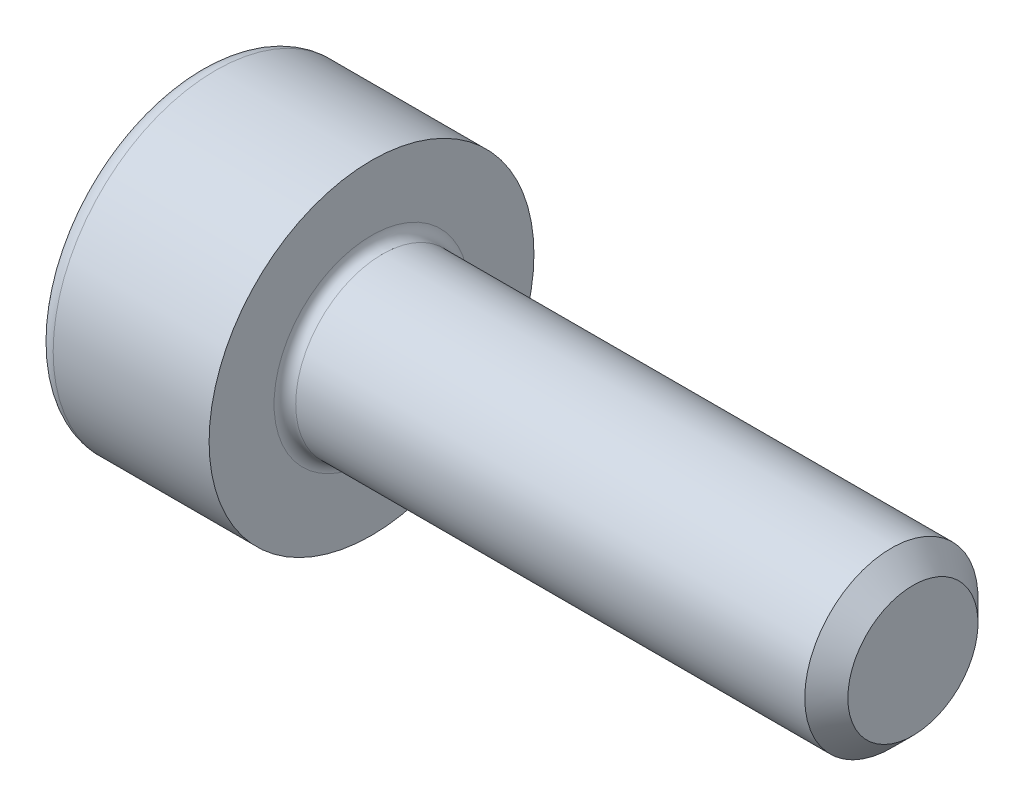
SolidWorks part; units mm, degrees
revolve "Base-Revolve" add sketch "BodySke"
sketch "BodySke" plane through (0, 0, 0) normal (0, 0, 1) x (1, 0, 0)
  line L0 (0, 0) -> (0, 1.5)
  line L1 (0, 1.5) -> (1.6, 1.5)
  line L2 (1.6, 1.5) -> (1.6, 0.8)
  line L3 (1.6, 0.8) -> (6.401, 0.8)
  line L4 (6.6, 0.601) -> (6.6, 0)
  line L5 (6.6, 0) -> (0, 0)
  line L6 (-31.75, 0) -> (127, 0) construction
  line L8 (6.6, 0.601) -> (6.401, 0.8)
  line L10 (6.6, -0.601) -> (6.401, -0.8) construction
  line L11 (1.95, 9.525) -> (1.95, 3.175) construction
  line L12 (0.6, 9.525) -> (0.6, 3.175) construction
  line L13 (-53.4, 9.525) -> (-53.4, 3.175) construction
  dimension "Diameter" = 1.6
  dimension "Head_dia" = 3
cosmetic thread "ThreadCosmetic" [suppressed]
fillet "Fillet1" radius 0.1 1 edges at (1.6, 0, 0.8)
fillet "Fillet2" radius 0.16 1 edges at (0, 0, 1.5)
ref_plane "Plane1" through (0, 0, 0) normal (0, 0, 1) x (1, 0, 0)
ref_plane "Plane2" through (0, 0, 0) normal (0, 1, 0) x (1, 0, 0)
ref_plane "Plane3" through (0, 0, 0) normal (1, 0, 0) x (0, 0, -1)
sketch "Sketch2" plane through (0, 0, 0) normal (0, 0, 1) x (1, 0, 0)
  line L0 (0, 0.76) -> (0.7, 0.76)
  line L1 (0.7, 0.76) -> (1.1388, 0)
  line L2 (-31.75, 0) -> (127, 0) construction
  line L3 (1.1388, 0) -> (0, 0)
  line L4 (0, 0) -> (0, 0.76)
  line L6 (0, 0) -> (47.625, 0) construction
  dimension "D1" = 0.76
  dimension "D2" = 60
revolve "Hex-PreBroach" cut sketch "Sketch2" angle 360 about L6
sketch "Sketch3" plane through (0, 0, 0) normal (-1, 0, 0) x (0, 0.5, 0.866)
  line L0 (0.4388, 0.76) -> (-0.4388, 0.76)
  line L1 (-0.4388, 0.76) -> (-0.8776, 0)
  line L2 (0.4388, 0.76) -> (0.8776, 0)
  line L3 (0.4388, -0.76) -> (0.8776, 0)
  line L4 (0.4388, -0.76) -> (-0.4388, -0.76)
  line L5 (-0.4388, -0.76) -> (-0.8776, 0)
  dimension "D1" = 0.76
  dimension "D2" = 0.76
extrude "Hex" cut sketch "Sketch3" against normal blind 0.7
sketch "ThdSchSke" plane through (0, 0, 0) normal (0, 0, 1) x (1, 0, 0)
  line L0 (2.65, -0.601) -> (2.5107, -0.8)
  line L1 (2.65, -0.601) -> (2.7893, -0.8)
  line L2 (2.7893, -0.8) -> (2.7893, -1)
  line L3 (-3.175, 0) -> (5.1513, 0) construction
  line L4 (0, 1.34) -> (0, -1.34) construction
  line L5 (2.7893, -1) -> (2.5107, -1)
  line L6 (2.5107, -1) -> (2.5107, -0.8)
  dimension "Diameter" = 1.6
  dimension "Thread_minor" = 1.202
  dimension "Start" = 2.65
revolve "ThreadSchematic" [suppressed] cut sketch "ThdSchSke" angle 360 about L3
pattern_linear "ThdSchPat" [suppressed]
equation "\"D2@Sketch3\" = \"Hex_size@Sketch3\" / 2"
equation "\"D1@Sketch3\" = \"Hex_size@Sketch3\" / 2"
equation "\"D1@Sketch2\" = \"Hex_size@Sketch3\" / 2"
equation "\"Thread_minor@ThreadCosmetic\"  =  \"Minor_dia@BodySke\""
equation "\"Depth@Sketch2\" =  \"Key_eng@Hex\""
equation "\"Thread_length@ThreadCosmetic\" = ((sgn( (\"Length@BodySke\" - \"Advance@BodySke\" * 3.0) - \"Thread_nom@BodySke\" )-1)*( (\"Length@BodySke\" - \"Advance@BodySke\" * 3.0) - \"Thread_nom@BodySke\" ))/-2+ \"Thread_nom@BodySke\""
equation "\"Thread_minor@ThdSchSke\" = \"Minor_dia@BodySke\""
equation "\"Diameter@ThdSchSke\" = \"Diameter@BodySke\""
equation "\"Overcut@ThdSchSke\" = \"Diameter@BodySke\" * 1.25"
equation "\"Start@ThdSchSke\" = \"Head_ht@BodySke\" + \"Length@BodySke\" - \"Thread_length@ThreadCosmetic\"  '---Non-countersunk---"
equation "\"Num_threads@ThdSchPat\" = int( \"Thread_length@ThreadCosmetic\" / \"Advance@BodySke\" + 0.999 )  + 1"
equation "\"Advance@ThdSchPat\" = \"Thread_length@ThreadCosmetic\" /  (\"Num_threads@ThdSchPat\" - 1) 'relax it"
equation "\"Num_threads@ThdSchPat\" = \"Num_threads@ThdSchPat\" - sgn( \"Num_threads@ThdSchPat\" - 1) '---chamfered tips only---"
